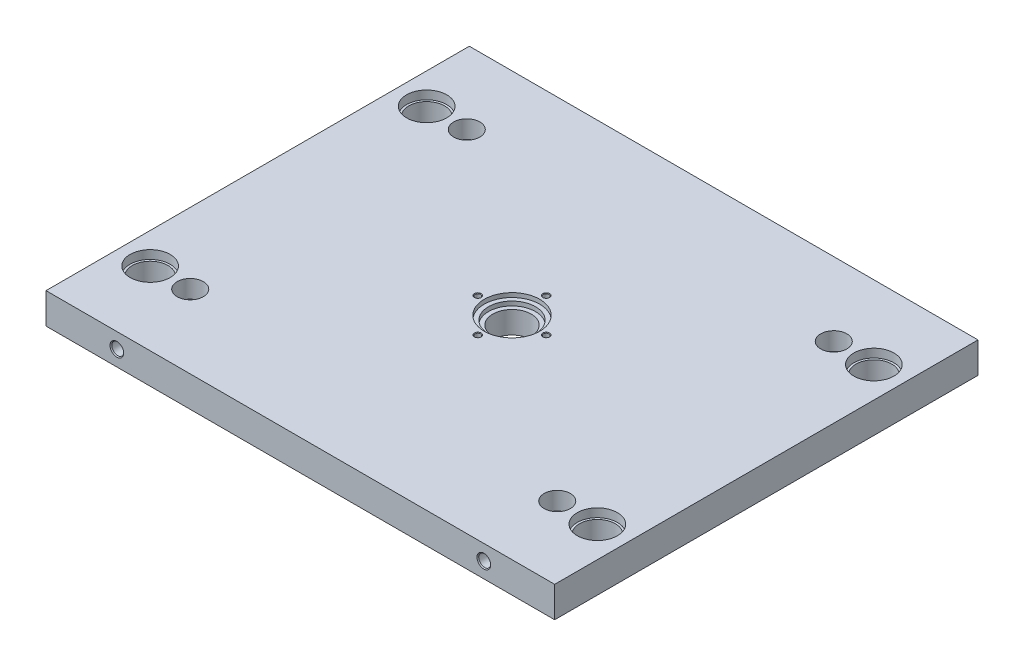
SolidWorks part; units mm, degrees
material "1.2312 (40CrMnMoS8-6)"
ref_plane "Płaszczyzna przednia" through (0, 0, 0) normal (0, 0, 1) x (1, 0, 0)
ref_plane "Płaszczyzna górna" through (0, 0, 0) normal (0, 1, 0) x (1, 0, 0)
ref_plane "Płaszczyzna prawa" through (0, 0, 0) normal (1, 0, 0) x (0, 0, -1)
sketch "Szkic1" plane through (0, 0, 0) normal (0, 1, 0) x (1, 0, 0)
  line L0 (298, 496) -> (298, 0) construction
  line L1 (0, 496) -> (596, 496)
  line L2 (0, 496) -> (0, 0)
  line L3 (0, 0) -> (596, 0)
  line L4 (596, 496) -> (596, 0)
  line L5 (0, 248) -> (596, 248) construction
  circle A0 centre (36, 410) radius 21
  circle A1 centre (560, 410) radius 21
  circle A2 centre (560, 86) radius 21
  circle A3 centre (36, 86) radius 21
  circle A4 centre (298, 248) radius 45
  dimension "D3" = 524
  dimension "D4" = 324
  dimension "D1" = 596
  dimension "D2" = 496
extrude "Dodanie-wyciągnięcie1" add sketch "Szkic1" against normal blind 36 contours A4 | L4 L1 L2 L3 A4 A1 A0 A2 A3 region at (298, 0, -488.2461) region at (298, 0, -248)
sketch "Szkic6" plane through (0, 0, 0) normal (0, 1, 0) x (1, 0, 0)
  line L1 (83, 410) -> (513, 410)
  line L2 (83, 410) -> (83, 86)
  line L3 (83, 86) -> (513, 86)
  line L4 (513, 410) -> (513, 86)
  line L5 (298, 496) -> (298, 0) construction
  line L6 (0, 248) -> (596, 248) construction
  dimension "D1" = 430
  dimension "D2" = 324
  dimension "D3" = 215
  dimension "D4" = 162
hole_wizard "Pogłębienie walcowe pod M16 Wkręt z łbem sześciokątnym z gniazdem2" positions "Szkic 3D5" profile "Szkic7" counterbore size "M16" standard "ISO" end condition through all
sketch3d "Szkic 3D5"
  point P0 (83, 0, -410)
  point P3 (513, 0, -410)
  point P6 (513, 0, -86)
  point P9 (83, 0, -86)
sketch "Szkic7" plane through (83, 0, -410) normal (1, 0, 0) x (0, 0, 1)
  line L0 (0, 0) -> (0, 36)
  line L1 (0, 36) -> (8.75, 36)
  line L3 (8.75, 36) -> (8.75, 21)
  line L4 (8.75, 21) -> (15.3565, 21)
  line L5 (15.3565, 21) -> (15.3565, 0)
  line L7 (15.3565, 0) -> (0, 0)
  line L11 (0, -6.35) -> (0, 107.95) construction
  dimension "Średnica otworu na wylot" = 17.5
  dimension "Głębokość otworu na wylot" = 36
  dimension "Średnica pogłębienia walcowego" = 30.713
  dimension "Głębokość pogłębienia walcowego" = 21
sketch "Szkic8" plane through (0, 0, 0) normal (0, 1, 0) x (1, 0, 0)
  line L0 (0, 248) -> (596, 248) construction
  line L1 (298, 496) -> (298, 0) construction
  line L2 (0, 496) -> (596, 496) construction
  circle A0 centre (36, 410) radius 23.5
  circle A1 centre (560, 410) radius 23.5
  circle A2 centre (560, 86) radius 23.5
  circle A3 centre (36, 86) radius 23.5
extrude "Wytnij-wyciągnięcie1" cut sketch "Szkic8" against normal blind 10
sketch "Szkic10" plane through (0, 0, 0) normal (0, 1, 0) x (1, 0, 0)
  line L0 (298, 496) -> (298, 0) construction
  line L1 (0, 496) -> (596, 496) construction
  line L2 (0, 0) -> (596, 0) construction
  circle A0 centre (298, 248) radius 22.5
  circle A1 centre (298, 248) radius 27.5
  circle A2 centre (298, 248) radius 32.5
  dimension "D1" = 65
  dimension "D2" = 55
  dimension "D3" = 45
extrude "Wytnij-wyciągnięcie3" cut sketch "Szkic10" against normal through all contours A0 L0 | L0 A0 region at (307.5493, 0, -248) region at (288.4507, 0, -248)
extrude "Wytnij-wyciągnięcie4" cut sketch "Szkic10<3>" against normal blind 10 contours L0 A1 A0 | A1 L0 A0 region at (317.0106, 0, -267.0106) region at (297.3851, 0, -273)
sketch "Szkic10<3>" plane through (0, 0, 0) normal (0, 1, 0) x (1, 0, 0) same geometry as "Szkic10"
extrude "Wytnij-wyciągnięcie5" cut sketch "Szkic10<4>" against normal blind 5 contours A2 L0 A1 | L0 A2 A1 region at (320.4671, 0, -270.4671) region at (297.2733, 0, -278)
sketch "Szkic10<4>" plane through (0, 0, 0) normal (0, 1, 0) x (1, 0, 0) same geometry as "Szkic10"
sketch "Szkic11" plane through (0, 0, 0) normal (0, 0, 1) x (1, 0, 0)
  line L0 (596, -18) -> (0, -18) construction
  line L1 (596, -36) -> (596, 0) construction
  line L2 (0, -36) -> (0, 0) construction
  line L3 (298, -18) -> (298, -36) construction
  line L4 (0, -36) -> (596, -36) construction
  point P10 (513, -18)
  point P11 (83, -18)
  dimension "D1" = 430
hole_wizard "Otwór gwintowany M161" positions "Szkic 3D6" profile "Szkic12" tap size "M16" standard "ISO"
sketch3d "Szkic 3D6"
  point P0 (513, -18, 0)
  point P3 (83, -18, 0)
sketch "Szkic12" plane through (513, -18, 0) normal (1, 0, 0) x (0, -1, 0)
  line L0 (0, 0) -> (0, 46.206)
  line L1 (0, 46.206) -> (7, 42)
  line L2 (7, 42) -> (7, 1.025)
  line L3 (7, 1.025) -> (8.025, 0)
  line L5 (8.025, 0) -> (0, 0)
  line L6 (-7, 1.025) -> (-8.025, 0) construction
  line L10 (0, 46.206) -> (-7, 42) construction
  line L11 (0, -6.35) -> (0, 107.95) construction
  dimension "Średnica wiertła gwintu" = 14
  dimension "Głębokość otworu gwintowanego" = 42
  dimension "Średnica zewnętrznego pogłębienia stożkowego" = 16.05
  dimension "Kąt zewnętrznego pogłębienia stożkowego" = 90
  dimension "Kąt wiertła" = 118
cosmetic thread "Gwint otworu1" parameters "D1"=32, "D2"=16
cosmetic thread "Gwint otworu2" parameters "D1"=32, "D2"=16
sketch "Szkic13" plane through (0, 0, 0) normal (0, 1, 0) x (1, 0, 0)
  circle A0 centre (298, 248) radius 40
  point P3 (298, 288)
  point P4 (258, 248)
  point P5 (298, 208)
  point P6 (338, 248)
hole_wizard "Otwór gwintowany M81" positions "Szkic 3D7" profile "Szkic14" tap size "M8" standard "ISO"
sketch3d "Szkic 3D7"
  point P0 (258, 0, -248)
  point P3 (298, 0, -288)
  point P6 (338, 0, -248)
  point P9 (298, 0, -208)
sketch "Szkic14" plane through (258, 0, -248) normal (1, 0, 0) x (0, 0, 1)
  line L0 (0, 0) -> (0, 24.2929)
  line L1 (0, 24.2929) -> (3.4, 22.25)
  line L2 (3.4, 22.25) -> (3.4, 0.625)
  line L3 (3.4, 0.625) -> (4.025, 0)
  line L5 (4.025, 0) -> (0, 0)
  line L6 (-3.4, 0.625) -> (-4.025, 0) construction
  line L10 (0, 24.2929) -> (-3.4, 22.25) construction
  line L11 (0, -6.35) -> (0, 107.95) construction
  dimension "Średnica wiertła gwintu" = 6.8
  dimension "Głębokość otworu gwintowanego" = 22.25
  dimension "Średnica zewnętrznego pogłębienia stożkowego" = 8.05
  dimension "Kąt zewnętrznego pogłębienia stożkowego" = 90
  dimension "Kąt wiertła" = 118
cosmetic thread "Gwint otworu3" parameters "D1"=16, "D2"=8
cosmetic thread "Gwint otworu4" parameters "D1"=16, "D2"=8
cosmetic thread "Gwint otworu5" parameters "D1"=16, "D2"=8
cosmetic thread "Gwint otworu6" parameters "D1"=16, "D2"=8
